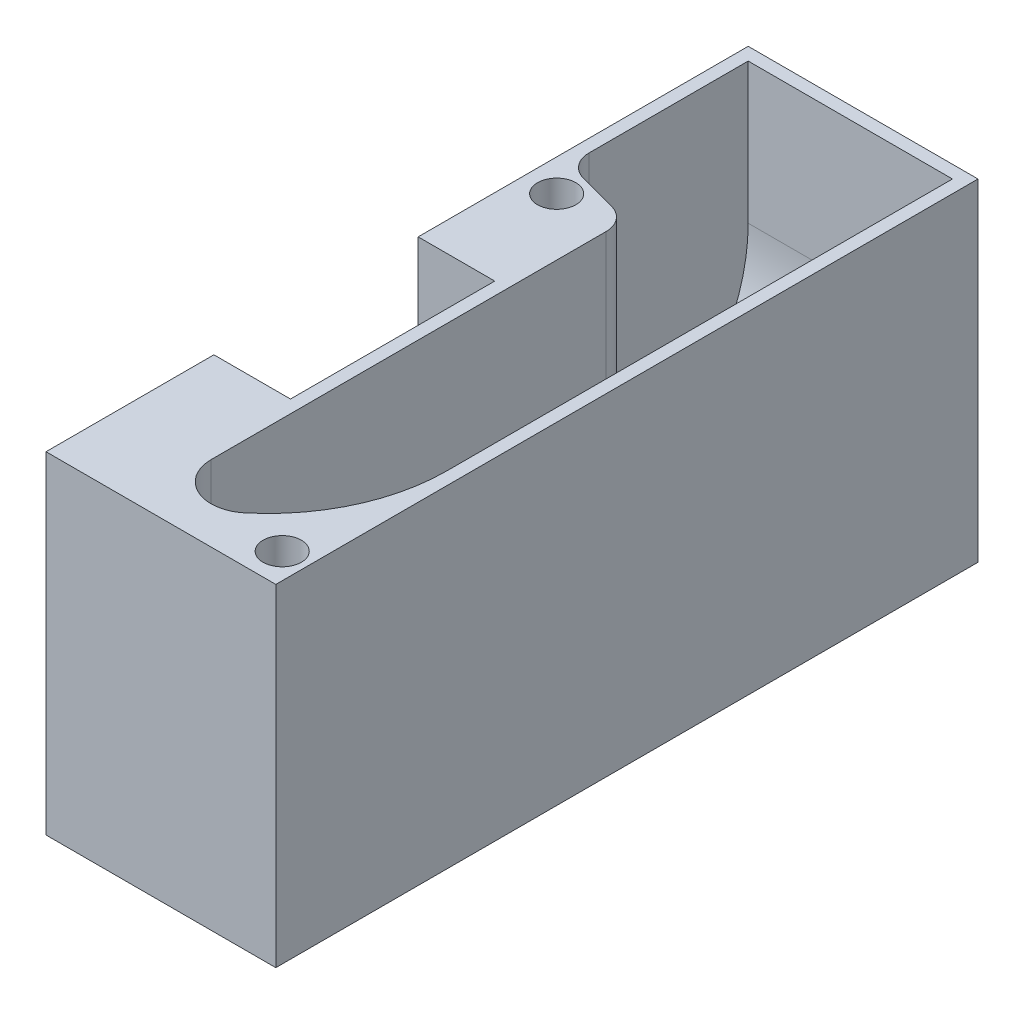
SolidWorks part; units mm, degrees
ref_plane "Front Plane" through (0, 0, 0) normal (0, 0, 1) x (1, 0, 0)
ref_plane "Top Plane" through (0, 0, 0) normal (0, 1, 0) x (1, 0, 0)
ref_plane "Right Plane" through (0, 0, 0) normal (1, 0, 0) x (0, 0, -1)
sketch "Sketch2" plane through (0, 0, 0) normal (0, -1, 0) x (1, 0, 0)
  line L0 (0, 0) -> (13, 0) construction
  line L18 (7, -9.15) -> (7, -35)
  line L20 (7, -35) -> (25, -35)
  line L21 (25, -35) -> (25, 20)
  line L22 (25, 20) -> (7, 20)
  line L23 (7, 20) -> (7, 6.85)
  line L24 (7, 6.85) -> (13, 6.85)
  line L25 (13, 6.85) -> (13, -9.15)
  line L26 (13, -9.15) -> (7, -9.15)
  point P1 (5.9865, 8.0481)
  point P3 (0, 0)
  point P4 (7.453, -35)
  point P13 (7.5, -8.5673)
  point P14 (7, 6.3704)
  dimension "D1" = 13
  dimension "D2" = 16
  dimension "D3" = 25
  dimension "D4" = 20
  dimension "D5" = 7
  dimension "D6" = 55
  dimension "D7" = 9.15
extrude "Boss-Extrude2" add sketch "Sketch2" along normal blind 26 separate body
shell "Shell1" thickness 1 removed face at (13, 0, -4.325)
fillet "Fillet1" radius 14 1 edges at (16, -25, -34)
sketch "Sketch3" plane through (0, 0, 0) normal (0, 1, 0) x (1, 0, 0)
  line L0 (14, 10.15) -> (8, 10.15)
  line L1 (8, 10.15) -> (8, 20)
  line L2 (8, 20) -> (14, 18.3923)
  line L3 (14, 18.3923) -> (14, 10.15)
  line L4 (24, 20) -> (8, 20) construction
  line L5 (14, -7.85) -> (8, -7.85)
  line L6 (14, -7.85) -> (14, -19)
  line L7 (14, -19) -> (8, -19)
  line L8 (8, -7.85) -> (8, -19)
  line L9 (11, -19) -> (11, -7.85) construction
  line L10 (14, -13.425) -> (8, -13.425) construction
  line L11 (8, 10.15) -> (8, 20) construction
  point P11 (8.5, 9)
  point P12 (0, 0)
  point P13 (8, 9)
  point P14 (8, 20)
  point P139 (11, -13.425)
  dimension "D1" = 75
extrude "Boss-Extrude3" add sketch "Sketch3" against normal up to next
fillet "Fillet2" radius 14 1 edges at (24, -12.5, 19)
sketch "Sketch7" plane through (0, 0, 0) normal (0, 1, 0) x (1, 0, 0)
  line L0 (9.5, 17.5) -> (9.5, -17.5) construction
  line L1 (9.5, -17.5) -> (23, -17.5) construction
  line L2 (0, 0) -> (9.5, 0) construction
  circle A0 centre (23, -17.5) radius 1.5
  circle A1 centre (9.5, 17.5) radius 1.5
  dimension "D4" = 3
  dimension "D1" = 9.5
  dimension "D2" = 35
  dimension "D3" = 13.5
extrude "Cut-Extrude2" cut sketch "Sketch7" against normal blind 3
fillet "Fillet3" radius 3 1 edges at (14, -12.5, 19)
fillet "Fillet4" [suppressed] radius 2
fillet "Fillet5" radius 2 2 edges at (14, -12.5, -18.3923) (8, -12.5, -20)
sketch "Sketch4" plane through (7, 0, 0) normal (-1, 0, 0) x (0, 0, 1)
  line L0 (10.35, -23) -> (-12.65, -23) construction
  line L1 (-1.15, -26) -> (-1.15, -23) construction
  line L4 (6.85, -26) -> (-9.15, -26) construction
  circle A0 centre (-12.65, -23) radius 2
  circle A1 centre (10.35, -23) radius 2
  point P6 (-1.15, -26)
  dimension "D1" = 4
  dimension "D2" = 23
  dimension "D3" = 3
extrude "Cut-Extrude1" cut sketch "Sketch4" against normal blind 9
